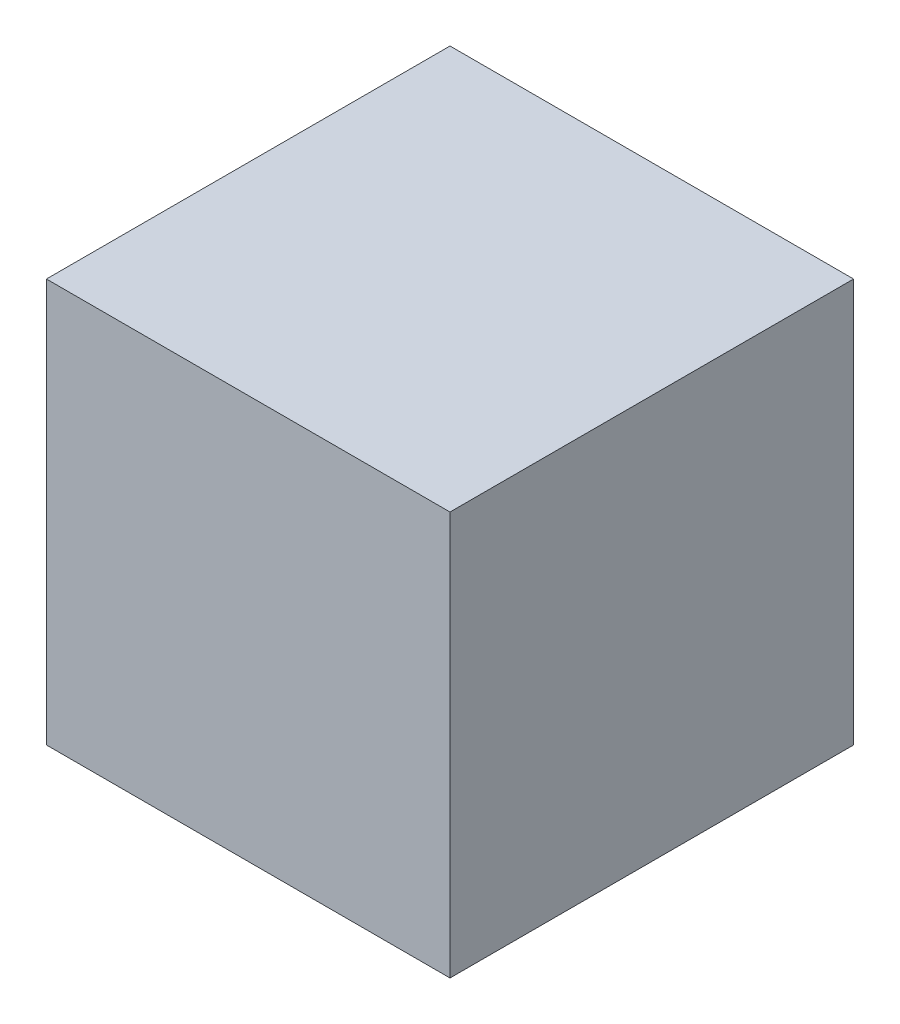
SolidWorks part; units mm, degrees
ref_plane "Front Plane" through (0, 0, 0) normal (0, 0, 1) x (1, 0, 0)
ref_plane "Top Plane" through (0, 0, 0) normal (0, 1, 0) x (1, 0, 0)
ref_plane "Right Plane" through (0, 0, 0) normal (1, 0, 0) x (0, 0, -1)
sketch "Sketch1" plane through (0, 0, 0) normal (0, 0, 1) x (1, 0, 0)
  line L1 (-30, 30) -> (30, 30)
  line L2 (-30, 30) -> (-30, -30)
  line L3 (-30, -30) -> (30, -30)
  line L4 (30, 30) -> (30, -30)
  line L5 (-30, 30) -> (30, -30) construction
  line L6 (-30, -30) -> (30, 30) construction
  point P0 (0, 0)
  dimension "D1" = 60
  dimension "D2" = 60
extrude "Boss-Extrude1" add sketch "Sketch1" along normal blind 60
